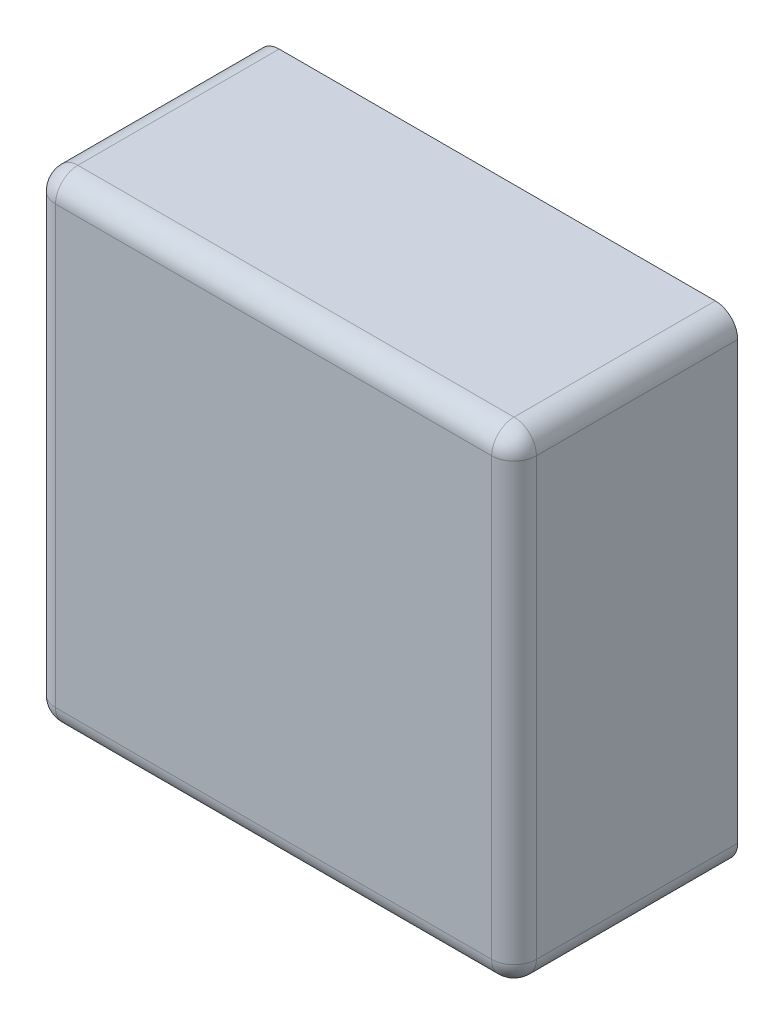
SolidWorks part; units mm, degrees
ref_plane "Piano frontale" through (0, 0, 0) normal (0, 0, 1) x (1, 0, 0)
ref_plane "Piano superiore" through (0, 0, 0) normal (0, 1, 0) x (1, 0, 0)
ref_plane "Piano destro" through (0, 0, 0) normal (1, 0, 0) x (0, 0, -1)
sketch "Schizzo1" plane through (0, 0, 0) normal (0, 0, 1) x (1, 0, 0)
  line L1 (0, 0) -> (43, 0)
  line L2 (0, 0) -> (0, 43)
  line L3 (0, 43) -> (43, 43)
  line L4 (43, 0) -> (43, 43)
  dimension "D1" = 43
  dimension "D2" = 43
extrude "Estrusione-Estrusione1" add sketch "Schizzo1" along normal blind 20
shell "Svuota2" thickness 1 removed face at (21.5, 21.5, 0)
sketch "Schizzo3" plane through (0, 0, 0) normal (0, -1, 0) x (-1, 0, 0)
  line L1 (-33.8358, -18.5076) -> (-40.3107, -18.5076)
  line L2 (-33.8358, -18.5076) -> (-33.8358, -14.9194)
  line L3 (-33.8358, -14.9194) -> (-40.3107, -14.9194)
  line L4 (-40.3107, -18.5076) -> (-40.3107, -14.9194)
  dimension "D1" = 6.4749
  dimension "D2" = 3.5882
extrude "Taglio-Estrusione1" cut sketch "Schizzo3" against normal blind 2
sketch "Schizzo4" plane through (0, 0, 0) normal (0, -1, 0) x (1, 0, 0)
  line L1 (4.8518, 17.1077) -> (22.1796, 17.1077)
  line L2 (4.8518, 17.1077) -> (4.8518, 11.7474)
  line L3 (4.8518, 11.7474) -> (22.1796, 11.7474)
  line L4 (22.1796, 17.1077) -> (22.1796, 11.7474)
extrude "Taglio-Estrusione2" cut sketch "Schizzo4" against normal blind 1
sketch "Schizzo8" plane through (0, 0, 0) normal (0, -1, 0) x (1, 0, 0)
  line L1 (26.6545, 8.5466) -> (37.1545, 8.5466)
  line L2 (26.6545, 8.5466) -> (26.6545, 6.5466)
  line L3 (26.6545, 6.5466) -> (37.1545, 6.5466)
  line L4 (37.1545, 8.5466) -> (37.1545, 6.5466)
  dimension "D1" = 10.5
  dimension "D2" = 2
extrude "Taglio-Estrusione3" cut sketch "Schizzo8" against normal blind 1
fillet "Raccordo3" radius 2 7 edges at (21.5, 0, 20) (43, 21.5, 20) (0, 0, 10) (0, 21.5, 20) (43, 43, 10) (21.5, 43, 20) (0, 43, 10) tangent propagation no
fillet "Raccordo4" radius 2 2 edges at (42.4142, 0.5858, 19.4142) (43, 0, 9)
fillet "Raccordo5" radius 0.5 4 edges at (1, 1, 9.5) (42, 1, 9.5) (1, 42, 9.5) (42, 42, 9.5)
